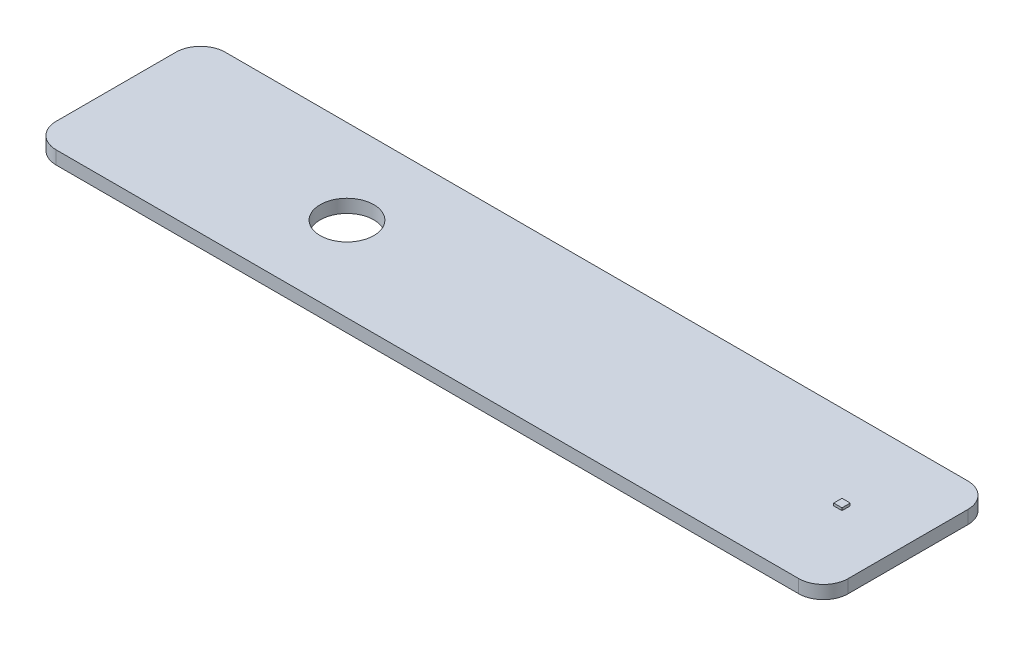
SolidWorks part; units mm, degrees
material "Custom Plastic"
ref_plane "Front Plane" through (0, 0, 0) normal (0, 0, 1) x (1, 0, 0)
ref_plane "Top Plane" through (0, 0, 0) normal (0, 1, 0) x (1, 0, 0)
ref_plane "Right Plane" through (0, 0, 0) normal (1, 0, 0) x (0, 0, -1)
sketch "Sketch1" plane through (0, 0, 0) normal (0, 1, 0) x (1, 0, 0)
  line L1 (-45, 10.25) -> (45, 10.25)
  line L2 (-48, 7.25) -> (-48, -7.25)
  line L3 (-45, -10.25) -> (45, -10.25)
  line L4 (48, 7.25) -> (48, -7.25)
  line L5 (-48, 10.25) -> (48, -10.25) construction
  line L6 (-48, -10.25) -> (48, 10.25) construction
  arc A0 (-48, -7.25) -> (-45, -10.25) centre (-45, -7.25) ccw
  arc A1 (45, -10.25) -> (48, -7.25) centre (45, -7.25) ccw
  arc A2 (45, 10.25) -> (48, 7.25) centre (45, 7.25) cw
  arc A3 (-45, 10.25) -> (-48, 7.25) centre (-45, 7.25) ccw
  point P0 (0, 0)
  dimension "D3" = 3
  dimension "D1" = 96
  dimension "D2" = 20.5
extrude "Boss-Extrude1" add sketch "Sketch1" along normal blind 1.6 contours L3 A1 L4 A2 L1 A3 L2 A0
sketch "Sketch2" plane through (0, 1.6, 0) normal (0, 1, 0) x (1, 0, 0)
  line L1 (39.5, 0.5) -> (40.5, 0.5)
  line L2 (39.5, 0.5) -> (39.5, -0.5)
  line L3 (39.5, -0.5) -> (40.5, -0.5)
  line L4 (40.5, 0.5) -> (40.5, -0.5)
  line L5 (39.5, 0.5) -> (40.5, -0.5) construction
  line L6 (39.5, -0.5) -> (40.5, 0.5) construction
  line L7 (-48, 0) -> (48, 0) construction
  line L8 (-48, 7.25) -> (-48, -7.25) construction
  line L9 (48, 7.25) -> (48, -7.25) construction
  point P0 (40, 0)
  dimension "D1" = 1
  dimension "D2" = 1
  dimension "D3" = 88
extrude "Boss-Extrude2" add sketch "Sketch2" along normal blind 0.3 contours L3 L4 L1 L2
sketch "Sketch3" plane through (0, 1.6, 0) normal (0, 1, 0) x (1, 0, 0)
  line L0 (-48, 7.25) -> (-48, -7.25) construction
  line L1 (-45, -10.25) -> (45, -10.25) construction
  circle A0 centre (-20, 0) radius 3.25
  dimension "D1" = 6.5
  dimension "D2" = 28
  dimension "D3" = 10.25
extrude "Cut-Extrude1" cut sketch "Sketch3" against normal through all
